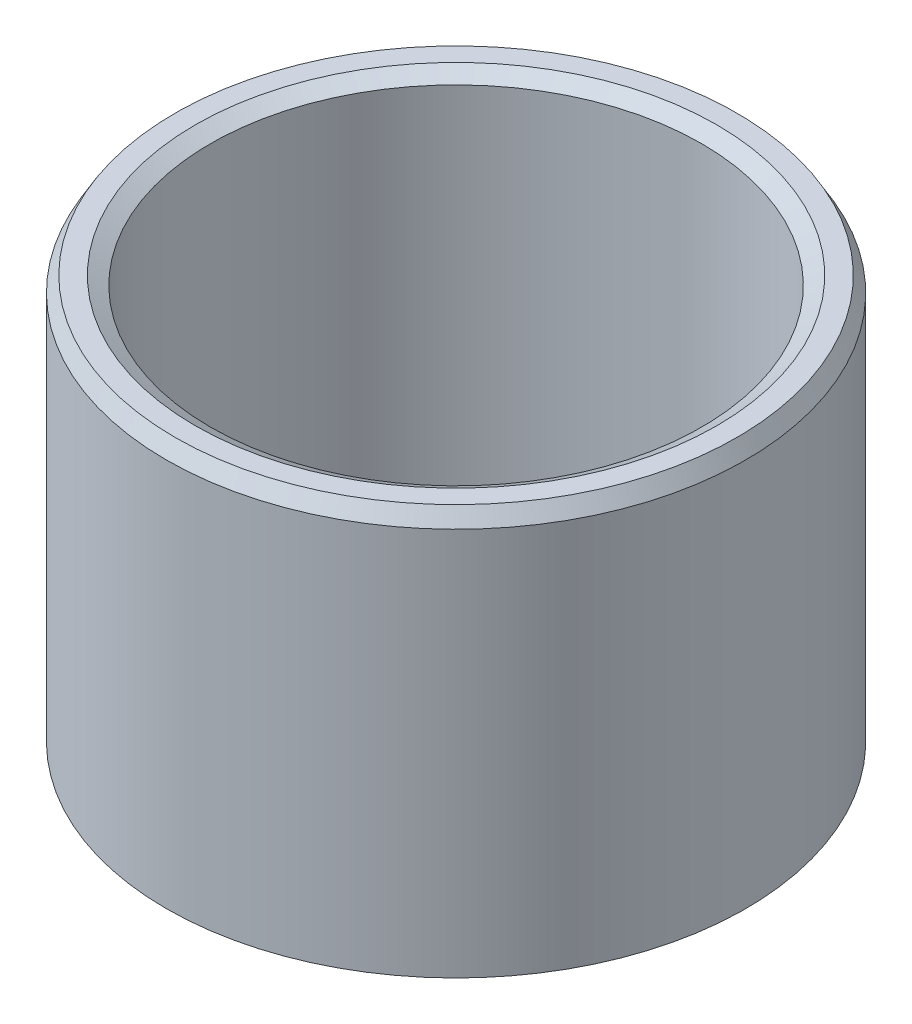
SolidWorks part; units mm, degrees
ref_plane "Front Plane" through (0, 0, 0) normal (0, 0, 1) x (1, 0, 0)
ref_plane "Top Plane" through (0, 0, 0) normal (0, 1, 0) x (1, 0, 0)
ref_plane "Right Plane" through (0, 0, 0) normal (1, 0, 0) x (0, 0, -1)
sketch "Sketch1" plane through (0, 0, 0) normal (0, 1, 0) x (1, 0, 0)
  circle A0 centre (0, 0) radius 60
  dimension "SLEEVE_OD" = 120
extrude "Boss-Extrude1" add sketch "Sketch1" along normal blind 85.4439
sketch "Sketch2" plane through (0, 0, 0) normal (0, 1, 0) x (1, 0, 0)
  circle A0 centre (0, 0) radius 50.8651
  dimension "BORE_D" = 101.7301
extrude "Cut-Extrude1" cut sketch "Sketch2" along normal through all
chamfer "Chamfer1" distance 3.1374 angle 30 4 edges at (0, 85.4439, 50.8651) (0, 0, 50.8651) (0, 0, 60) (0, 85.4439, 60) first distance on face at (0, 85.4439, 50.8651) first distance on face at (0, 0, 50.8651) first distance on face at (0, 85.4439, 60)
